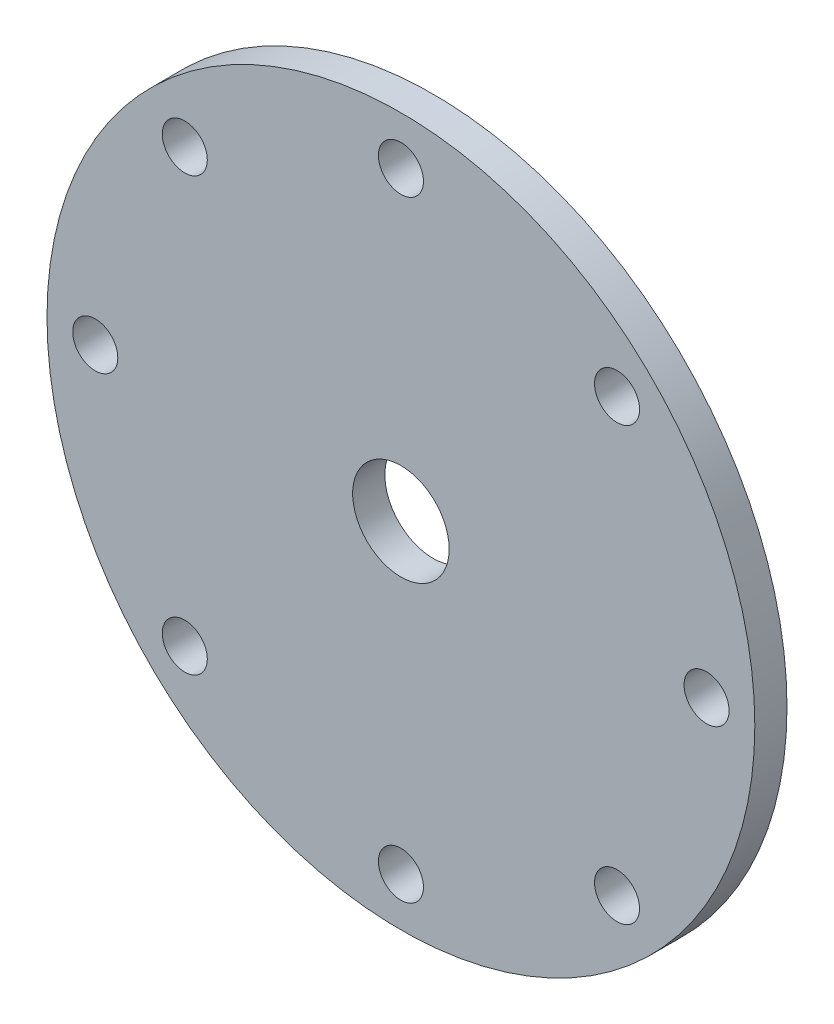
SolidWorks part; units mm, degrees
ref_plane "Front Plane" through (0, 0, 0) normal (0, 0, 1) x (1, 0, 0)
ref_plane "Top Plane" through (0, 0, 0) normal (0, 1, 0) x (1, 0, 0)
ref_plane "Right Plane" through (0, 0, 0) normal (1, 0, 0) x (0, 0, -1)
sketch "Sketch1" plane through (0, 0, 0) normal (0, 0, 1) x (1, 0, 0)
  circle A0 centre (0, 0) radius 55
  circle A1 centre (0, 0) radius 7.5
  circle A2 centre (0, 47.5) radius 3.5
  circle A3 centre (0, -47.5) radius 3.5
  circle A6 centre (33.5876, 33.5876) radius 3.5
  circle A7 centre (47.5, 0) radius 3.5
  circle A8 centre (33.5876, -33.5876) radius 3.5
  circle A9 centre (0, -47.5) radius 3.5
  circle A10 centre (-33.5876, -33.5876) radius 3.5
  circle A11 centre (-47.5, 0) radius 3.5
  circle A12 centre (-33.5876, 33.5876) radius 3.5
  point P7 (0, 0)
  dimension "D1" = 110
  dimension "D2" = 15
  dimension "D3" = 7
  dimension "D4" = 47.5
  dimension "D5" = 8
extrude "Boss-Extrude2" add sketch "Sketch1" along normal blind 5 contours A0 A12 A11 A10 A8 A7 A6 A1 A2 A3 region at (-53.4444, 0, 0)
